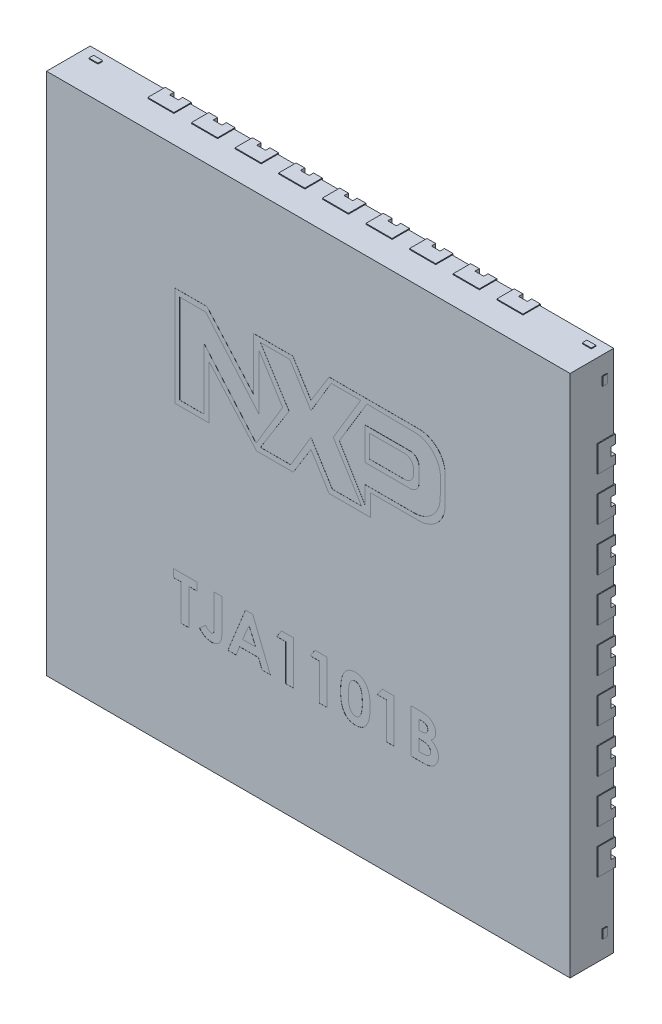
SolidWorks part; units mm, degrees
ref_plane "Front Plane" through (0, 0, 0) normal (0, 0, 1) x (1, 0, 0)
ref_plane "Top Plane" through (0, 0, 0) normal (0, 1, 0) x (1, 0, 0)
ref_plane "Right Plane" through (0, 0, 0) normal (1, 0, 0) x (0, 0, -1)
sketch "Sketch1" plane through (0, 0, 0) normal (0, 0, 1) x (1, 0, 0)
  line L1 (3, -3) -> (-3, -3)
  line L2 (3, -3) -> (3, 3)
  line L3 (3, 3) -> (-3, 3)
  line L4 (-3, -3) -> (-3, 3)
  line L5 (3, -3) -> (-3, 3) construction
  line L6 (3, 3) -> (-3, -3) construction
  point P0 (0, 0)
  dimension "D1" = 6
  dimension "D2" = 6
extrude "Boss-Extrude1" add sketch "Sketch1" along normal blind 0.5
sketch "Sketch3" plane through (0, 0, 0.5) normal (0, 0, 1) x (1, 0, 0)
  line L1 (-1.8824, 1.9808) -> (1.8824, 1.9808)
  line L2 (-1.8824, 1.9808) -> (-1.8824, -1.9808)
  line L3 (-1.8824, -1.9808) -> (1.8824, -1.9808)
  line L4 (1.8824, 1.9808) -> (1.8824, -1.9808)
  line L5 (-1.8824, 1.9808) -> (1.8824, -1.9808) construction
  line L6 (-1.8824, -1.9808) -> (1.8824, 1.9808) construction
  point P0 (0, 0)
sketch "Sketch4" plane through (0, 0, 0) normal (0, 0, -1) x (-1, 0, 0)
  line L0 (1.8824, 1.9808) -> (-1.8824, 1.9808) construction
  line L1 (-1.6324, 1.9808) -> (1.6324, 1.9808)
  line L2 (-1.8824, 1.7308) -> (-1.8824, -1.7308)
  line L3 (-1.6324, -1.9808) -> (1.6324, -1.9808)
  line L5 (-1.8824, 1.9808) -> (1.8824, -1.9808) construction
  line L6 (-1.8824, -1.9808) -> (1.8824, 1.9808) construction
  line L7 (-1.8824, 1.9808) -> (-1.8824, -1.9808) construction
  line L8 (1.8824, 1.7308) -> (1.8824, 1.4732)
  line L9 (1.8824, 1.9808) -> (1.8824, -1.9808) construction
  line L10 (1.8824, 0.8432) -> (1.8824, -1.7308)
  arc A0 (1.6324, -1.9808) -> (1.8824, -1.7308) centre (1.6324, -1.7308) ccw
  arc A1 (-1.8824, -1.7308) -> (-1.6324, -1.9808) centre (-1.6324, -1.7308) ccw
  arc A2 (1.6324, 1.9808) -> (1.8824, 1.7308) centre (1.6324, 1.7308) cw
  arc A3 (-1.6324, 1.9808) -> (-1.8824, 1.7308) centre (-1.6324, 1.7308) ccw
  arc A4 (1.8127, 1.3779) -> (1.8127, 0.9385) centre (1.8824, 1.1582) ccw
  arc A5 (1.8127, 0.9385) -> (1.8824, 0.8432) centre (1.7824, 0.8432) cw
  arc A6 (1.8824, 1.4732) -> (1.8127, 1.3779) centre (1.7824, 1.4732) cw
  point P0 (0, 0)
  point P29 (1.8824, 0.9277)
  point P32 (1.8824, 1.3887)
  dimension "D3" = 0.25
  dimension "D4" = 0.1
  dimension "D1" = 0
  dimension "D2" = 0
extrude "Cut-Extrude2" cut sketch "Sketch4" against normal blind 0.001
sketch "Sketch6" plane through (0, 0, 0.5) normal (0, 0, 1) x (1, 0, 0)
  line L0 (70.7212, 256.7277) -> (518.7212, 256.7277) construction
  line L1 (-1.5243, 0.4405) -> (-1.5243, 1.584)
  line L2 (-1.5243, 1.584) -> (-1.1608, 1.584)
  line L3 (-1.1608, 1.584) -> (-0.6294, 0.983)
  line L4 (-0.6294, 0.983) -> (-0.6294, 1.584)
  line L5 (-0.6294, 1.584) -> (-0.1766, 1.584)
  line L6 (-0.1766, 1.584) -> (0.0315, 1.2485)
  line L7 (0.0315, 1.2485) -> (0.2387, 1.584)
  line L8 (0.2387, 1.584) -> (1.269, 1.584)
  line L9 (1.569, 1.284) -> (1.569, 0.9732)
  line L10 (1.269, 0.6732) -> (0.7132, 0.6732)
  line L11 (0.7132, 0.6732) -> (0.7132, 0.4288)
  line L12 (0.7132, 0.4288) -> (0.2387, 0.4288)
  line L13 (0.2387, 0.4288) -> (0.0315, 0.7628)
  line L14 (0.0315, 0.7628) -> (-0.1711, 0.4347)
  line L15 (-0.1711, 0.4347) -> (-0.5917, 0.4347)
  line L16 (-0.5917, 0.4347) -> (-1.1363, 1.0506)
  line L17 (-1.1363, 1.0506) -> (-1.1363, 0.4405)
  line L18 (-1.1363, 0.4405) -> (-1.5243, 0.4405)
  line L19 (-1.4732, 0.4992) -> (-1.4732, 1.5224)
  line L20 (-1.4732, 1.5224) -> (-1.1742, 1.5224)
  line L21 (-1.1742, 1.5224) -> (-0.5652, 0.815)
  line L22 (-0.5652, 0.815) -> (-0.5652, 1.4509)
  line L23 (-0.5652, 1.4509) -> (-0.2935, 1.0155)
  line L24 (-0.2935, 1.0155) -> (-0.5981, 0.5087)
  line L25 (-0.5981, 0.5087) -> (-1.1917, 1.1983)
  line L26 (-1.1917, 1.1983) -> (-1.1917, 0.4992)
  line L27 (-1.1917, 0.4992) -> (-1.4732, 0.4992)
  line L28 (-0.5484, 1.5343) -> (-0.2103, 1.5343)
  line L29 (-0.2103, 1.5343) -> (0.0315, 1.1473)
  line L30 (0.0315, 1.1473) -> (0.2635, 1.5343)
  line L31 (0.2635, 1.5343) -> (0.6011, 1.5343)
  line L32 (0.6011, 1.5343) -> (0.2868, 1.0101)
  line L33 (0.2868, 1.0101) -> (0.6118, 0.4899)
  line L34 (0.6118, 0.4899) -> (0.2765, 0.4899)
  line L35 (0.2765, 0.4899) -> (0.0315, 0.882)
  line L36 (0.0315, 0.882) -> (-0.2015, 0.4933)
  line L37 (-0.2015, 0.4933) -> (-0.5484, 0.4933)
  line L38 (-0.5484, 0.4933) -> (-0.2196, 1.0155)
  line L39 (-0.2196, 1.0155) -> (-0.5484, 1.5343)
  line L40 (0.6733, 1.5343) -> (1.2198, 1.5266)
  line L41 (1.5155, 1.2225) -> (1.5127, 1.0185)
  line L42 (1.2127, 0.7227) -> (0.6509, 0.7227)
  line L43 (0.6509, 0.7227) -> (0.6509, 0.5207)
  line L44 (0.6509, 0.5207) -> (0.3558, 1.0101)
  line L45 (0.3558, 1.0101) -> (0.6733, 1.5343)
  line L47 (0.6509, 1.3152) -> (1.169, 1.3152)
  line L48 (1.269, 1.2152) -> (1.269, 1.0433)
  line L49 (1.169, 0.9433) -> (0.6509, 0.9433)
  line L50 (0.6509, 1.3152) -> (0.6509, 0.9433)
  line L51 (0.7044, 1.2599) -> (1.1068, 1.2599)
  line L52 (0.7044, 1.2599) -> (0.7044, 1.0022)
  line L53 (0.7044, 1.0022) -> (1.1068, 1.0022)
  line L54 (1.2068, 1.1599) -> (1.2068, 1.1022)
  arc A0 (1.569, 0.9732) -> (1.269, 0.6732) centre (1.269, 0.9732) cw
  arc A1 (1.269, 1.584) -> (1.569, 1.284) centre (1.269, 1.284) cw
  arc A2 (1.5127, 1.0185) -> (1.2127, 0.7227) centre (1.2127, 1.0227) cw
  arc A3 (1.2198, 1.5266) -> (1.5155, 1.2225) centre (1.2156, 1.2267) cw
  arc A4 (1.1068, 1.0022) -> (1.2068, 1.1022) centre (1.1068, 1.1022) ccw
  arc A5 (1.1068, 1.2599) -> (1.2068, 1.1599) centre (1.1068, 1.1599) cw
  arc A6 (1.269, 1.0433) -> (1.169, 0.9433) centre (1.169, 1.0433) cw
  arc A7 (1.169, 1.3152) -> (1.269, 1.2152) centre (1.169, 1.2152) cw
  dimension "D1" = 0.3
  dimension "D2" = 0.3
  dimension "D3" = 0.1
extrude "Boss-Extrude2" add sketch "Sketch6" along normal blind 0.001 contours A1 L8 L7 L6 L5 L4 L3 L2 L1 L18 L17 L16 L15 L14 L13 L12 L11 L10 A0 L9 L38 L39 L28 L29 L30 L31 L32 L33 L34 L35 L36 L37 L26 L27 L19 L20 L21 L22 L23 L24 L25 L40 A3 L41 A2 L42 L43 L44 | L52 L51 A5 L54 A4 L53 region at (-1.4913, 1.0122, 0.5)
sketch "Sketch8" plane through (0, 0, 0.5) normal (0, 0, 1) x (1, 0, 0)
  line L0 (-1.5539, -1.7085) -> (2.0877, -1.7085) construction
  text T0 "<b>TJA1101B</b>" font "Century Gothic" height 0.5
extrude "Cut-Extrude3" cut sketch "Sketch8" against normal blind 0.001
sketch "Sketch2" plane through (0, 0, 0) normal (0, 0, -1) x (-1, 0, 0)
  line L0 (-2, 2.65) -> (-2, 3.35) construction
  line L1 (-2.15, 2.65) -> (-2.15, 3.35)
  line L2 (-1.85, 2.65) -> (-1.85, 3.35)
  line L3 (-1.35, 2.65) -> (-1.35, 3.35)
  line L6 (-3, 3) -> (3, 3) construction
  line L7 (-1.65, 2.65) -> (-1.65, 3.35)
  line L8 (-1.5, 2.65) -> (-1.5, 3.35) construction
  line L9 (-0.85, 2.65) -> (-0.85, 3.35)
  line L10 (-1.15, 2.65) -> (-1.15, 3.35)
  line L11 (-1, 2.65) -> (-1, 3.35) construction
  line L12 (-0.35, 2.65) -> (-0.35, 3.35)
  line L13 (-0.65, 2.65) -> (-0.65, 3.35)
  line L14 (-0.5, 2.65) -> (-0.5, 3.35) construction
  line L15 (0.15, 2.65) -> (0.15, 3.35)
  line L16 (-0.15, 2.65) -> (-0.15, 3.35)
  line L17 (0, 2.65) -> (0, 3.35) construction
  line L18 (0.65, 2.65) -> (0.65, 3.35)
  line L19 (0.35, 2.65) -> (0.35, 3.35)
  line L20 (0.5, 2.65) -> (0.5, 3.35) construction
  line L21 (1.15, 2.65) -> (1.15, 3.35)
  line L22 (0.85, 2.65) -> (0.85, 3.35)
  line L23 (1, 2.65) -> (1, 3.35) construction
  line L24 (1.65, 2.65) -> (1.65, 3.35)
  line L25 (1.35, 2.65) -> (1.35, 3.35)
  line L26 (1.5, 2.65) -> (1.5, 3.35) construction
  line L27 (2.15, 2.65) -> (2.15, 3.35)
  line L28 (1.85, 2.65) -> (1.85, 3.35)
  line L29 (2, 2.65) -> (2, 3.35) construction
  line L30 (0, 0) -> (0, -1.6259) construction
  line L31 (0, 0) -> (1.65, 0) construction
  line L32 (-2, -2.65) -> (-2, -3.35) construction
  line L33 (-2.15, -2.65) -> (-2.15, -3.35)
  line L34 (-1.85, -2.65) -> (-1.85, -3.35)
  line L35 (-1.5, -2.65) -> (-1.5, -3.35) construction
  line L36 (-1.65, -2.65) -> (-1.65, -3.35)
  line L37 (-1.35, -2.65) -> (-1.35, -3.35)
  line L38 (-1, -2.65) -> (-1, -3.35) construction
  line L39 (-1.15, -2.65) -> (-1.15, -3.35)
  line L40 (-0.85, -2.65) -> (-0.85, -3.35)
  line L41 (-0.5, -2.65) -> (-0.5, -3.35) construction
  line L42 (-0.65, -2.65) -> (-0.65, -3.35)
  line L43 (-0.35, -2.65) -> (-0.35, -3.35)
  line L44 (0, -2.65) -> (0, -3.35) construction
  line L45 (-0.15, -2.65) -> (-0.15, -3.35)
  line L46 (0.15, -2.65) -> (0.15, -3.35)
  line L47 (0.5, -2.65) -> (0.5, -3.35) construction
  line L48 (0.35, -2.65) -> (0.35, -3.35)
  line L49 (0.65, -2.65) -> (0.65, -3.35)
  line L50 (1, -2.65) -> (1, -3.35) construction
  line L51 (0.85, -2.65) -> (0.85, -3.35)
  line L52 (1.15, -2.65) -> (1.15, -3.35)
  line L53 (1.5, -2.65) -> (1.5, -3.35) construction
  line L54 (1.35, -2.65) -> (1.35, -3.35)
  line L55 (1.65, -2.65) -> (1.65, -3.35)
  line L56 (2, -2.65) -> (2, -3.35) construction
  line L57 (1.85, -2.65) -> (1.85, -3.35)
  line L58 (2.15, -2.65) -> (2.15, -3.35)
  line L59 (2.65, 2) -> (3.35, 2) construction
  line L61 (-2.65, 2) -> (-3.35, 2) construction
  line L62 (-2.65, 2.15) -> (-3.35, 2.15)
  line L63 (-2.65, 1.85) -> (-3.35, 1.85)
  line L64 (-2.65, 1.5) -> (-3.35, 1.5) construction
  line L65 (-2.65, 1.65) -> (-3.35, 1.65)
  line L66 (-2.65, 1.35) -> (-3.35, 1.35)
  line L67 (-2.65, 1) -> (-3.35, 1) construction
  line L68 (-2.65, 1.15) -> (-3.35, 1.15)
  line L69 (-2.65, 0.85) -> (-3.35, 0.85)
  line L70 (-2.65, 0.5) -> (-3.35, 0.5) construction
  line L71 (-2.65, 0.65) -> (-3.35, 0.65)
  line L72 (-2.65, 0.35) -> (-3.35, 0.35)
  line L73 (-2.65, 0) -> (-3.35, 0) construction
  line L74 (-2.65, 0.15) -> (-3.35, 0.15)
  line L75 (-2.65, -0.15) -> (-3.35, -0.15)
  line L76 (-2.65, -0.5) -> (-3.35, -0.5) construction
  line L77 (-2.65, -0.35) -> (-3.35, -0.35)
  line L78 (-2.65, -0.65) -> (-3.35, -0.65)
  line L79 (-2.65, -1) -> (-3.35, -1) construction
  line L80 (-2.65, -0.85) -> (-3.35, -0.85)
  line L81 (-2.65, -1.15) -> (-3.35, -1.15)
  line L82 (-2.65, -1.5) -> (-3.35, -1.5) construction
  line L83 (-2.65, -1.35) -> (-3.35, -1.35)
  line L84 (-2.65, -1.65) -> (-3.35, -1.65)
  line L85 (-2.65, -2) -> (-3.35, -2) construction
  line L86 (-2.65, -1.85) -> (-3.35, -1.85)
  line L87 (-2.65, -2.15) -> (-3.35, -2.15)
  line L88 (2.65, 2.15) -> (3.35, 2.15)
  line L89 (2.65, 1.85) -> (3.35, 1.85)
  line L90 (2.65, 1.5) -> (3.35, 1.5) construction
  line L91 (2.65, 1.65) -> (3.35, 1.65)
  line L92 (2.65, 1.35) -> (3.35, 1.35)
  line L93 (2.65, 1) -> (3.35, 1) construction
  line L94 (2.65, 1.15) -> (3.35, 1.15)
  line L95 (2.65, 0.85) -> (3.35, 0.85)
  line L96 (2.65, 0.5) -> (3.35, 0.5) construction
  line L97 (2.65, 0.65) -> (3.35, 0.65)
  line L98 (2.65, 0.35) -> (3.35, 0.35)
  line L99 (2.65, 0) -> (3.35, 0) construction
  line L100 (2.65, 0.15) -> (3.35, 0.15)
  line L101 (2.65, -0.15) -> (3.35, -0.15)
  line L102 (2.65, -0.5) -> (3.35, -0.5) construction
  line L103 (2.65, -0.35) -> (3.35, -0.35)
  line L104 (2.65, -0.65) -> (3.35, -0.65)
  line L105 (2.65, -1) -> (3.35, -1) construction
  line L106 (2.65, -0.85) -> (3.35, -0.85)
  line L107 (2.65, -1.15) -> (3.35, -1.15)
  line L108 (2.65, -1.5) -> (3.35, -1.5) construction
  line L109 (2.65, -1.35) -> (3.35, -1.35)
  line L110 (2.65, -1.65) -> (3.35, -1.65)
  line L111 (2.65, -2) -> (3.35, -2) construction
  line L112 (2.65, -1.85) -> (3.35, -1.85)
  line L113 (2.65, -2.15) -> (3.35, -2.15)
  arc A0 (-2.15, 2.65) -> (-1.85, 2.65) centre (-2, 2.65) ccw
  arc A1 (-1.85, 3.35) -> (-2.15, 3.35) centre (-2, 3.35) ccw
  arc A4 (-1.65, 2.65) -> (-1.35, 2.65) centre (-1.5, 2.65) ccw
  arc A5 (-1.35, 3.35) -> (-1.65, 3.35) centre (-1.5, 3.35) ccw
  arc A6 (-1.15, 2.65) -> (-0.85, 2.65) centre (-1, 2.65) ccw
  arc A7 (-0.85, 3.35) -> (-1.15, 3.35) centre (-1, 3.35) ccw
  arc A8 (-0.65, 2.65) -> (-0.35, 2.65) centre (-0.5, 2.65) ccw
  arc A9 (-0.35, 3.35) -> (-0.65, 3.35) centre (-0.5, 3.35) ccw
  arc A10 (-0.15, 2.65) -> (0.15, 2.65) centre (0, 2.65) ccw
  arc A11 (0.15, 3.35) -> (-0.15, 3.35) centre (0, 3.35) ccw
  arc A12 (0.35, 2.65) -> (0.65, 2.65) centre (0.5, 2.65) ccw
  arc A13 (0.65, 3.35) -> (0.35, 3.35) centre (0.5, 3.35) ccw
  arc A14 (0.85, 2.65) -> (1.15, 2.65) centre (1, 2.65) ccw
  arc A15 (1.15, 3.35) -> (0.85, 3.35) centre (1, 3.35) ccw
  arc A16 (1.35, 2.65) -> (1.65, 2.65) centre (1.5, 2.65) ccw
  arc A17 (1.65, 3.35) -> (1.35, 3.35) centre (1.5, 3.35) ccw
  arc A18 (1.85, 2.65) -> (2.15, 2.65) centre (2, 2.65) ccw
  arc A19 (2.15, 3.35) -> (1.85, 3.35) centre (2, 3.35) ccw
  arc A20 (-2.15, -2.65) -> (-1.85, -2.65) centre (-2, -2.65) cw
  arc A21 (-1.85, -3.35) -> (-2.15, -3.35) centre (-2, -3.35) cw
  arc A22 (-1.65, -2.65) -> (-1.35, -2.65) centre (-1.5, -2.65) cw
  arc A23 (-1.35, -3.35) -> (-1.65, -3.35) centre (-1.5, -3.35) cw
  arc A24 (-1.15, -2.65) -> (-0.85, -2.65) centre (-1, -2.65) cw
  arc A25 (-0.85, -3.35) -> (-1.15, -3.35) centre (-1, -3.35) cw
  arc A26 (-0.65, -2.65) -> (-0.35, -2.65) centre (-0.5, -2.65) cw
  arc A27 (-0.35, -3.35) -> (-0.65, -3.35) centre (-0.5, -3.35) cw
  arc A28 (-0.15, -2.65) -> (0.15, -2.65) centre (0, -2.65) cw
  arc A29 (0.15, -3.35) -> (-0.15, -3.35) centre (0, -3.35) cw
  arc A30 (0.35, -2.65) -> (0.65, -2.65) centre (0.5, -2.65) cw
  arc A31 (0.65, -3.35) -> (0.35, -3.35) centre (0.5, -3.35) cw
  arc A32 (0.85, -2.65) -> (1.15, -2.65) centre (1, -2.65) cw
  arc A33 (1.15, -3.35) -> (0.85, -3.35) centre (1, -3.35) cw
  arc A34 (1.35, -2.65) -> (1.65, -2.65) centre (1.5, -2.65) cw
  arc A35 (1.65, -3.35) -> (1.35, -3.35) centre (1.5, -3.35) cw
  arc A36 (1.85, -2.65) -> (2.15, -2.65) centre (2, -2.65) cw
  arc A37 (2.15, -3.35) -> (1.85, -3.35) centre (2, -3.35) cw
  arc A38 (-2.65, 2.15) -> (-2.65, 1.85) centre (-2.65, 2) cw
  arc A39 (-3.35, 1.85) -> (-3.35, 2.15) centre (-3.35, 2) cw
  arc A40 (-2.65, 1.65) -> (-2.65, 1.35) centre (-2.65, 1.5) cw
  arc A41 (-3.35, 1.35) -> (-3.35, 1.65) centre (-3.35, 1.5) cw
  arc A42 (-2.65, 1.15) -> (-2.65, 0.85) centre (-2.65, 1) cw
  arc A43 (-3.35, 0.85) -> (-3.35, 1.15) centre (-3.35, 1) cw
  arc A44 (-2.65, 0.65) -> (-2.65, 0.35) centre (-2.65, 0.5) cw
  arc A45 (-3.35, 0.35) -> (-3.35, 0.65) centre (-3.35, 0.5) cw
  arc A46 (-2.65, 0.15) -> (-2.65, -0.15) centre (-2.65, 0) cw
  arc A47 (-3.35, -0.15) -> (-3.35, 0.15) centre (-3.35, 0) cw
  arc A48 (-2.65, -0.35) -> (-2.65, -0.65) centre (-2.65, -0.5) cw
  arc A49 (-3.35, -0.65) -> (-3.35, -0.35) centre (-3.35, -0.5) cw
  arc A50 (-2.65, -0.85) -> (-2.65, -1.15) centre (-2.65, -1) cw
  arc A51 (-3.35, -1.15) -> (-3.35, -0.85) centre (-3.35, -1) cw
  arc A52 (-2.65, -1.35) -> (-2.65, -1.65) centre (-2.65, -1.5) cw
  arc A53 (-3.35, -1.65) -> (-3.35, -1.35) centre (-3.35, -1.5) cw
  arc A54 (-2.65, -1.85) -> (-2.65, -2.15) centre (-2.65, -2) cw
  arc A55 (-3.35, -2.15) -> (-3.35, -1.85) centre (-3.35, -2) cw
  arc A56 (2.65, 2.15) -> (2.65, 1.85) centre (2.65, 2) ccw
  arc A57 (3.35, 1.85) -> (3.35, 2.15) centre (3.35, 2) ccw
  arc A58 (2.65, 1.65) -> (2.65, 1.35) centre (2.65, 1.5) ccw
  arc A59 (3.35, 1.35) -> (3.35, 1.65) centre (3.35, 1.5) ccw
  arc A60 (2.65, 1.15) -> (2.65, 0.85) centre (2.65, 1) ccw
  arc A61 (3.35, 0.85) -> (3.35, 1.15) centre (3.35, 1) ccw
  arc A62 (2.65, 0.65) -> (2.65, 0.35) centre (2.65, 0.5) ccw
  arc A63 (3.35, 0.35) -> (3.35, 0.65) centre (3.35, 0.5) ccw
  arc A64 (2.65, 0.15) -> (2.65, -0.15) centre (2.65, 0) ccw
  arc A65 (3.35, -0.15) -> (3.35, 0.15) centre (3.35, 0) ccw
  arc A66 (2.65, -0.35) -> (2.65, -0.65) centre (2.65, -0.5) ccw
  arc A67 (3.35, -0.65) -> (3.35, -0.35) centre (3.35, -0.5) ccw
  arc A68 (2.65, -0.85) -> (2.65, -1.15) centre (2.65, -1) ccw
  arc A69 (3.35, -1.15) -> (3.35, -0.85) centre (3.35, -1) ccw
  arc A70 (2.65, -1.35) -> (2.65, -1.65) centre (2.65, -1.5) ccw
  arc A71 (3.35, -1.65) -> (3.35, -1.35) centre (3.35, -1.5) ccw
  arc A72 (2.65, -1.85) -> (2.65, -2.15) centre (2.65, -2) ccw
  arc A73 (3.35, -2.15) -> (3.35, -1.85) centre (3.35, -2) ccw
  point P2 (-2, 3)
  point P10 (-1.5, 3)
  point P16 (-2, 2.5)
  point P21 (-1, 3)
  point P28 (-0.5, 3)
  point P35 (0, 3)
  point P42 (0.5, 3)
  point P49 (1, 3)
  point P56 (1.5, 3)
  point P63 (2, 3)
  point P72 (-2, -3)
  point P79 (-1.5, -3)
  point P86 (-1, -3)
  point P93 (-0.5, -3)
  point P100 (0, -3)
  point P107 (0.5, -3)
  point P114 (1, -3)
  point P121 (1.5, -3)
  point P128 (2, -3)
  point P136 (3, 2)
  point P140 (-3, 2)
  point P147 (-3, 1.5)
  point P154 (-3, 1)
  point P161 (-3, 0.5)
  point P168 (-3, 0)
  point P175 (-3, -0.5)
  point P182 (-3, -1)
  point P189 (-3, -1.5)
  point P196 (-3, -2)
  point P206 (3, 1.5)
  point P213 (3, 1)
  point P220 (3, 0.5)
  point P227 (3, 0)
  point P234 (3, -0.5)
  point P241 (3, -1)
  point P248 (3, -1.5)
  point P255 (3, -2)
  dimension "D1" = 0.3
  dimension "D2" = 9
  dimension "D4" = 0
  dimension "D5" = 0.5
  dimension "D8" = 2
sketch "Sketch10" plane through (0, 0, 0.5) normal (0, 0, 1) x (1, 0, 0)
  line L0 (0.6509, 1.3152) -> (1.169, 1.3152)
  line L1 (0.6509, 1.3152) -> (0.6509, 0.9433)
  line L2 (0.6509, 0.9433) -> (1.169, 0.9433)
  line L3 (1.269, 1.2152) -> (1.269, 1.0433)
  line L4 (1.2068, 1.1599) -> (1.2068, 1.1022)
  line L5 (1.1068, 1.2599) -> (0.7044, 1.2599)
  line L6 (0.7044, 1.2599) -> (0.7044, 1.0022)
  line L7 (0.7044, 1.0022) -> (1.1068, 1.0022)
  arc A0 (1.169, 1.3152) -> (1.269, 1.2152) centre (1.169, 1.2152) cw
  arc A1 (1.269, 1.0433) -> (1.169, 0.9433) centre (1.169, 1.0433) cw
  arc A2 (1.2068, 1.1022) -> (1.1068, 1.0022) centre (1.1068, 1.1022) cw
  arc A3 (1.1068, 1.2599) -> (1.2068, 1.1599) centre (1.1068, 1.1599) cw
extrude "Boss-Extrude3" add sketch "Sketch10" along normal blind 0.002
extrude "Boss-Extrude4" add sketch "Sketch2" along normal blind 0.01
sketch "Sketch11" plane through (0, 0, 0.5) normal (0, 0, 1) x (1, 0, 0)
  line L1 (-3, 3) -> (3, 3)
  line L2 (-3, 3) -> (-3, -3)
  line L3 (-3, -3) -> (3, -3)
  line L4 (3, 3) -> (3, -3)
  line L5 (-4.69, 4.3097) -> (4.6689, 4.3097)
  line L6 (-4.69, 4.3097) -> (-4.69, -5.1125)
  line L7 (-4.69, -5.1125) -> (4.6689, -5.1125)
  line L8 (4.6689, 4.3097) -> (4.6689, -5.1125)
extrude "Cut-Extrude4" cut sketch "Sketch11" against normal blind 10.01
sketch "Sketch12" plane through (0, 0, -0.01) normal (0, 0, -1) x (-1, 0, 0)
  line L0 (-3, 3) -> (-1.6807, 1.6807) construction
  line L1 (-3, 3) -> (-2.15, 3) construction
  line L2 (0, 0) -> (0.5, 0) construction
  line L3 (0, 0) -> (0, 0.8589) construction
  circle A0 centre (-2, 2.65) radius 0.025
  circle A1 centre (-1.5, 2.65) radius 0.025
  circle A2 centre (-1, 2.65) radius 0.025
  circle A3 centre (-0.5, 2.65) radius 0.025
  circle A4 centre (0, 2.65) radius 0.025
  circle A5 centre (0.5, 2.65) radius 0.025
  circle A6 centre (1, 2.65) radius 0.025
  circle A7 centre (1.5, 2.65) radius 0.025
  circle A8 centre (2, 2.65) radius 0.025
  circle A9 centre (-2.65, -2) radius 0.025
  circle A10 centre (-2.65, -1.5) radius 0.025
  circle A11 centre (-2.65, -1) radius 0.025
  circle A12 centre (-2.65, -0.5) radius 0.025
  circle A13 centre (-2.65, 0) radius 0.025
  circle A14 centre (-2.65, 0.5) radius 0.025
  circle A15 centre (-2.65, 1) radius 0.025
  circle A16 centre (-2.65, 1.5) radius 0.025
  circle A17 centre (-2.65, 2) radius 0.025
  circle A18 centre (2, -2.65) radius 0.025
  circle A19 centre (1.5, -2.65) radius 0.025
  circle A20 centre (1, -2.65) radius 0.025
  circle A21 centre (0.5, -2.65) radius 0.025
  circle A22 centre (0, -2.65) radius 0.025
  circle A23 centre (-0.5, -2.65) radius 0.025
  circle A24 centre (-1, -2.65) radius 0.025
  circle A25 centre (-1.5, -2.65) radius 0.025
  circle A26 centre (-2, -2.65) radius 0.025
  circle A27 centre (2.65, 2) radius 0.025
  circle A28 centre (2.65, 1.5) radius 0.025
  circle A29 centre (2.65, 1) radius 0.025
  circle A30 centre (2.65, 0.5) radius 0.025
  circle A31 centre (2.65, 0) radius 0.025
  circle A32 centre (2.65, -0.5) radius 0.025
  circle A33 centre (2.65, -1) radius 0.025
  circle A34 centre (2.65, -1.5) radius 0.025
  circle A35 centre (2.65, -2) radius 0.025
  dimension "D1" = 0.05
  dimension "D3" = 45
  dimension "D2" = 9
sketch "Sketch14" plane through (0, -3, 0) normal (0, -1, 0) x (1, 0, 0)
  line L0 (-1.85, -0.01) -> (-1.85, 0) construction
  line L1 (-2.15, -0.01) -> (-1.85, -0.01)
  line L2 (-2.15, -0.01) -> (-2.15, 0.19)
  line L3 (-2.15, 0.19) -> (-1.85, 0.19)
  line L4 (-1.85, -0.01) -> (-1.85, 0.19)
  line L5 (-1.65, -0.01) -> (-1.65, 0.19)
  line L6 (-1.65, -0.01) -> (-1.35, -0.01)
  line L7 (-1.35, -0.01) -> (-1.35, 0.19)
  line L8 (-1.65, 0.19) -> (-1.35, 0.19)
  line L9 (-1.15, -0.01) -> (-1.15, 0.19)
  line L10 (-1.15, -0.01) -> (-0.85, -0.01)
  line L11 (-0.85, -0.01) -> (-0.85, 0.19)
  line L12 (-1.15, 0.19) -> (-0.85, 0.19)
  line L13 (-0.65, -0.01) -> (-0.65, 0.19)
  line L14 (-0.65, -0.01) -> (-0.35, -0.01)
  line L15 (-0.35, -0.01) -> (-0.35, 0.19)
  line L16 (-0.65, 0.19) -> (-0.35, 0.19)
  line L17 (-0.15, -0.01) -> (-0.15, 0.19)
  line L18 (-0.15, -0.01) -> (0.15, -0.01)
  line L19 (0.15, -0.01) -> (0.15, 0.19)
  line L20 (-0.15, 0.19) -> (0.15, 0.19)
  line L21 (0.35, -0.01) -> (0.35, 0.19)
  line L22 (0.35, -0.01) -> (0.65, -0.01)
  line L23 (0.65, -0.01) -> (0.65, 0.19)
  line L24 (0.35, 0.19) -> (0.65, 0.19)
  line L25 (0.85, -0.01) -> (0.85, 0.19)
  line L26 (0.85, -0.01) -> (1.15, -0.01)
  line L27 (1.15, -0.01) -> (1.15, 0.19)
  line L28 (0.85, 0.19) -> (1.15, 0.19)
  line L29 (1.35, -0.01) -> (1.35, 0.19)
  line L30 (1.35, -0.01) -> (1.65, -0.01)
  line L31 (1.65, -0.01) -> (1.65, 0.19)
  line L32 (1.35, 0.19) -> (1.65, 0.19)
  line L33 (1.85, -0.01) -> (1.85, 0.19)
  line L34 (1.85, -0.01) -> (2.15, -0.01)
  line L35 (2.15, -0.01) -> (2.15, 0.19)
  line L36 (1.85, 0.19) -> (2.15, 0.19)
  dimension "D1" = 0
  dimension "D2" = 0.2
  dimension "D3" = 9
extrude "Boss-Extrude5" add sketch "Sketch14" along normal blind 0.01
sketch "Sketch15" plane through (-3, 0, 0) normal (-1, 0, 0) x (0, 0, 1)
  line L0 (-0.01, -1.65) -> (-0.01, -1.35)
  line L1 (-0.01, -2.15) -> (0.19, -2.15)
  line L2 (-0.01, -2.15) -> (-0.01, -1.85)
  line L3 (-0.01, -1.85) -> (0.19, -1.85)
  line L4 (0.19, -2.15) -> (0.19, -1.85)
  line L5 (-0.01, -1.65) -> (0.19, -1.65)
  line L6 (0.19, -1.65) -> (0.19, -1.35)
  line L7 (-0.01, -1.35) -> (0.19, -1.35)
  line L8 (-0.01, -1.15) -> (-0.01, -0.85)
  line L9 (-0.01, -1.15) -> (0.19, -1.15)
  line L10 (0.19, -1.15) -> (0.19, -0.85)
  line L11 (-0.01, -0.85) -> (0.19, -0.85)
  line L12 (-0.01, -0.65) -> (-0.01, -0.35)
  line L13 (-0.01, -0.65) -> (0.19, -0.65)
  line L14 (0.19, -0.65) -> (0.19, -0.35)
  line L15 (-0.01, -0.35) -> (0.19, -0.35)
  line L16 (-0.01, -0.15) -> (-0.01, 0.15)
  line L17 (-0.01, -0.15) -> (0.19, -0.15)
  line L18 (0.19, -0.15) -> (0.19, 0.15)
  line L19 (-0.01, 0.15) -> (0.19, 0.15)
  line L20 (-0.01, 0.35) -> (-0.01, 0.65)
  line L21 (-0.01, 0.35) -> (0.19, 0.35)
  line L22 (0.19, 0.35) -> (0.19, 0.65)
  line L23 (-0.01, 0.65) -> (0.19, 0.65)
  line L24 (-0.01, 0.85) -> (-0.01, 1.15)
  line L25 (-0.01, 0.85) -> (0.19, 0.85)
  line L26 (0.19, 0.85) -> (0.19, 1.15)
  line L27 (-0.01, 1.15) -> (0.19, 1.15)
  line L28 (-0.01, 1.35) -> (-0.01, 1.65)
  line L29 (-0.01, 1.35) -> (0.19, 1.35)
  line L30 (0.19, 1.35) -> (0.19, 1.65)
  line L31 (-0.01, 1.65) -> (0.19, 1.65)
  line L32 (-0.01, 1.85) -> (-0.01, 2.15)
  line L33 (-0.01, 1.85) -> (0.19, 1.85)
  line L34 (0.19, 1.85) -> (0.19, 2.15)
  line L35 (-0.01, 2.15) -> (0.19, 2.15)
  dimension "D1" = 0
  dimension "D2" = 0.2
  dimension "D3" = 9
extrude "Boss-Extrude6" add sketch "Sketch15" along normal blind 0.01
mirror "Mirror1" about plane through (0, 0, 0) normal (1, 0, 0) of "Boss-Extrude6"
mirror "Mirror2" about plane through (0, 0, 0) normal (0, 1, 0) of "Boss-Extrude5"
sketch "Sketch16" plane through (0, 0, -0.01) normal (0, 0, -1) x (-1, 0, 0)
  line L0 (-2, 3.06) -> (-2, 2.96) construction
  line L1 (-1.85, 3.01) -> (-2.15, 3.01) construction
  line L2 (-1.95, 3.06) -> (-1.95, 2.96)
  line L3 (-2.05, 3.06) -> (-2.05, 2.96)
  line L4 (-1.55, 3.06) -> (-1.55, 2.96)
  line L5 (-1.45, 3.06) -> (-1.45, 2.96)
  line L6 (-1.5, 3.06) -> (-1.5, 2.96) construction
  line L7 (-1.05, 3.06) -> (-1.05, 2.96)
  line L8 (-0.95, 3.06) -> (-0.95, 2.96)
  line L9 (-1, 3.06) -> (-1, 2.96) construction
  line L10 (-0.55, 3.06) -> (-0.55, 2.96)
  line L11 (-0.45, 3.06) -> (-0.45, 2.96)
  line L12 (-0.5, 3.06) -> (-0.5, 2.96) construction
  line L13 (-0.05, 3.06) -> (-0.05, 2.96)
  line L14 (0.05, 3.06) -> (0.05, 2.96)
  line L15 (0, 3.06) -> (0, 2.96) construction
  line L16 (0.45, 3.06) -> (0.45, 2.96)
  line L17 (0.55, 3.06) -> (0.55, 2.96)
  line L18 (0.5, 3.06) -> (0.5, 2.96) construction
  line L19 (0.95, 3.06) -> (0.95, 2.96)
  line L20 (1.05, 3.06) -> (1.05, 2.96)
  line L21 (1, 3.06) -> (1, 2.96) construction
  line L22 (1.45, 3.06) -> (1.45, 2.96)
  line L23 (1.55, 3.06) -> (1.55, 2.96)
  line L24 (1.5, 3.06) -> (1.5, 2.96) construction
  line L25 (1.95, 3.06) -> (1.95, 2.96)
  line L26 (2.05, 3.06) -> (2.05, 2.96)
  line L27 (2, 3.06) -> (2, 2.96) construction
  line L28 (0, 0) -> (0.7795, 0) construction
  line L29 (0, 0) -> (0, 0.8504) construction
  line L30 (-2, -3.06) -> (-2, -2.96) construction
  line L31 (-1.95, -3.06) -> (-1.95, -2.96)
  line L32 (-2.05, -3.06) -> (-2.05, -2.96)
  line L33 (-1.5, -3.06) -> (-1.5, -2.96) construction
  line L34 (-1.45, -3.06) -> (-1.45, -2.96)
  line L35 (-1.55, -3.06) -> (-1.55, -2.96)
  line L36 (-1, -3.06) -> (-1, -2.96) construction
  line L37 (-0.95, -3.06) -> (-0.95, -2.96)
  line L38 (-1.05, -3.06) -> (-1.05, -2.96)
  line L39 (-0.5, -3.06) -> (-0.5, -2.96) construction
  line L40 (-0.45, -3.06) -> (-0.45, -2.96)
  line L41 (-0.55, -3.06) -> (-0.55, -2.96)
  line L42 (0, -3.06) -> (0, -2.96) construction
  line L43 (0.05, -3.06) -> (0.05, -2.96)
  line L44 (-0.05, -3.06) -> (-0.05, -2.96)
  line L45 (0.5, -3.06) -> (0.5, -2.96) construction
  line L46 (0.55, -3.06) -> (0.55, -2.96)
  line L47 (0.45, -3.06) -> (0.45, -2.96)
  line L48 (1, -3.06) -> (1, -2.96) construction
  line L49 (1.05, -3.06) -> (1.05, -2.96)
  line L50 (0.95, -3.06) -> (0.95, -2.96)
  line L51 (1.5, -3.06) -> (1.5, -2.96) construction
  line L52 (1.55, -3.06) -> (1.55, -2.96)
  line L53 (1.45, -3.06) -> (1.45, -2.96)
  line L54 (2, -3.06) -> (2, -2.96) construction
  line L55 (2.05, -3.06) -> (2.05, -2.96)
  line L56 (1.95, -3.06) -> (1.95, -2.96)
  line L57 (-3.06, 2) -> (-2.96, 2) construction
  line L58 (-3.01, 2.15) -> (-3.01, 1.85) construction
  line L59 (-3.06, 2.05) -> (-2.96, 2.05)
  line L60 (-3.06, 1.95) -> (-2.96, 1.95)
  line L61 (-3.06, 1.45) -> (-2.96, 1.45)
  line L62 (-3.06, 1.55) -> (-2.96, 1.55)
  line L63 (-3.06, 1.5) -> (-2.96, 1.5) construction
  line L64 (-3.06, 0.95) -> (-2.96, 0.95)
  line L65 (-3.06, 1.05) -> (-2.96, 1.05)
  line L66 (-3.06, 1) -> (-2.96, 1) construction
  line L67 (-3.06, 0.45) -> (-2.96, 0.45)
  line L68 (-3.06, 0.55) -> (-2.96, 0.55)
  line L69 (-3.06, 0.5) -> (-2.96, 0.5) construction
  line L70 (-3.06, -0.05) -> (-2.96, -0.05)
  line L71 (-3.06, 0.05) -> (-2.96, 0.05)
  line L72 (-3.06, 0) -> (-2.96, 0) construction
  line L73 (-3.06, -0.55) -> (-2.96, -0.55)
  line L74 (-3.06, -0.45) -> (-2.96, -0.45)
  line L75 (-3.06, -0.5) -> (-2.96, -0.5) construction
  line L76 (-3.06, -1.05) -> (-2.96, -1.05)
  line L77 (-3.06, -0.95) -> (-2.96, -0.95)
  line L78 (-3.06, -1) -> (-2.96, -1) construction
  line L79 (-3.06, -1.55) -> (-2.96, -1.55)
  line L80 (-3.06, -1.45) -> (-2.96, -1.45)
  line L81 (-3.06, -1.5) -> (-2.96, -1.5) construction
  line L82 (-3.06, -2.05) -> (-2.96, -2.05)
  line L83 (-3.06, -1.95) -> (-2.96, -1.95)
  line L84 (-3.06, -2) -> (-2.96, -2) construction
  line L85 (3.06, 2) -> (2.96, 2) construction
  line L86 (3.06, 2.05) -> (2.96, 2.05)
  line L87 (3.06, 1.95) -> (2.96, 1.95)
  line L88 (3.06, 1.5) -> (2.96, 1.5) construction
  line L89 (3.06, 1.55) -> (2.96, 1.55)
  line L90 (3.06, 1.45) -> (2.96, 1.45)
  line L91 (3.06, 1) -> (2.96, 1) construction
  line L92 (3.06, 1.05) -> (2.96, 1.05)
  line L93 (3.06, 0.95) -> (2.96, 0.95)
  line L94 (3.06, 0.5) -> (2.96, 0.5) construction
  line L95 (3.06, 0.55) -> (2.96, 0.55)
  line L96 (3.06, 0.45) -> (2.96, 0.45)
  line L97 (3.06, 0) -> (2.96, 0) construction
  line L98 (3.06, 0.05) -> (2.96, 0.05)
  line L99 (3.06, -0.05) -> (2.96, -0.05)
  line L100 (3.06, -0.5) -> (2.96, -0.5) construction
  line L101 (3.06, -0.45) -> (2.96, -0.45)
  line L102 (3.06, -0.55) -> (2.96, -0.55)
  line L103 (3.06, -1) -> (2.96, -1) construction
  line L104 (3.06, -0.95) -> (2.96, -0.95)
  line L105 (3.06, -1.05) -> (2.96, -1.05)
  line L106 (3.06, -1.5) -> (2.96, -1.5) construction
  line L107 (3.06, -1.45) -> (2.96, -1.45)
  line L108 (3.06, -1.55) -> (2.96, -1.55)
  line L109 (3.06, -2) -> (2.96, -2) construction
  line L110 (3.06, -1.95) -> (2.96, -1.95)
  line L111 (3.06, -2.05) -> (2.96, -2.05)
  arc A0 (-1.95, 3.06) -> (-2.05, 3.06) centre (-2, 3.06) ccw
  arc A1 (-2.05, 2.96) -> (-1.95, 2.96) centre (-2, 2.96) ccw
  arc A2 (-1.45, 3.06) -> (-1.55, 3.06) centre (-1.5, 3.06) ccw
  arc A3 (-1.55, 2.96) -> (-1.45, 2.96) centre (-1.5, 2.96) ccw
  arc A4 (-0.95, 3.06) -> (-1.05, 3.06) centre (-1, 3.06) ccw
  arc A5 (-1.05, 2.96) -> (-0.95, 2.96) centre (-1, 2.96) ccw
  arc A6 (-0.45, 3.06) -> (-0.55, 3.06) centre (-0.5, 3.06) ccw
  arc A7 (-0.55, 2.96) -> (-0.45, 2.96) centre (-0.5, 2.96) ccw
  arc A8 (0.05, 3.06) -> (-0.05, 3.06) centre (0, 3.06) ccw
  arc A9 (-0.05, 2.96) -> (0.05, 2.96) centre (0, 2.96) ccw
  arc A10 (0.55, 3.06) -> (0.45, 3.06) centre (0.5, 3.06) ccw
  arc A11 (0.45, 2.96) -> (0.55, 2.96) centre (0.5, 2.96) ccw
  arc A12 (1.05, 3.06) -> (0.95, 3.06) centre (1, 3.06) ccw
  arc A13 (0.95, 2.96) -> (1.05, 2.96) centre (1, 2.96) ccw
  arc A14 (1.55, 3.06) -> (1.45, 3.06) centre (1.5, 3.06) ccw
  arc A15 (1.45, 2.96) -> (1.55, 2.96) centre (1.5, 2.96) ccw
  arc A16 (2.05, 3.06) -> (1.95, 3.06) centre (2, 3.06) ccw
  arc A17 (1.95, 2.96) -> (2.05, 2.96) centre (2, 2.96) ccw
  arc A18 (-1.95, -3.06) -> (-2.05, -3.06) centre (-2, -3.06) cw
  arc A19 (-2.05, -2.96) -> (-1.95, -2.96) centre (-2, -2.96) cw
  arc A20 (-1.45, -3.06) -> (-1.55, -3.06) centre (-1.5, -3.06) cw
  arc A21 (-1.55, -2.96) -> (-1.45, -2.96) centre (-1.5, -2.96) cw
  arc A22 (-0.95, -3.06) -> (-1.05, -3.06) centre (-1, -3.06) cw
  arc A23 (-1.05, -2.96) -> (-0.95, -2.96) centre (-1, -2.96) cw
  arc A24 (-0.45, -3.06) -> (-0.55, -3.06) centre (-0.5, -3.06) cw
  arc A25 (-0.55, -2.96) -> (-0.45, -2.96) centre (-0.5, -2.96) cw
  arc A26 (0.05, -3.06) -> (-0.05, -3.06) centre (0, -3.06) cw
  arc A27 (-0.05, -2.96) -> (0.05, -2.96) centre (0, -2.96) cw
  arc A28 (0.55, -3.06) -> (0.45, -3.06) centre (0.5, -3.06) cw
  arc A29 (0.45, -2.96) -> (0.55, -2.96) centre (0.5, -2.96) cw
  arc A30 (1.05, -3.06) -> (0.95, -3.06) centre (1, -3.06) cw
  arc A31 (0.95, -2.96) -> (1.05, -2.96) centre (1, -2.96) cw
  arc A32 (1.55, -3.06) -> (1.45, -3.06) centre (1.5, -3.06) cw
  arc A33 (1.45, -2.96) -> (1.55, -2.96) centre (1.5, -2.96) cw
  arc A34 (2.05, -3.06) -> (1.95, -3.06) centre (2, -3.06) cw
  arc A35 (1.95, -2.96) -> (2.05, -2.96) centre (2, -2.96) cw
  arc A36 (-3.06, 2.05) -> (-3.06, 1.95) centre (-3.06, 2) ccw
  arc A37 (-2.96, 1.95) -> (-2.96, 2.05) centre (-2.96, 2) ccw
  arc A38 (-3.06, 1.55) -> (-3.06, 1.45) centre (-3.06, 1.5) ccw
  arc A39 (-2.96, 1.45) -> (-2.96, 1.55) centre (-2.96, 1.5) ccw
  arc A40 (-3.06, 1.05) -> (-3.06, 0.95) centre (-3.06, 1) ccw
  arc A41 (-2.96, 0.95) -> (-2.96, 1.05) centre (-2.96, 1) ccw
  arc A42 (-3.06, 0.55) -> (-3.06, 0.45) centre (-3.06, 0.5) ccw
  arc A43 (-2.96, 0.45) -> (-2.96, 0.55) centre (-2.96, 0.5) ccw
  arc A44 (-3.06, 0.05) -> (-3.06, -0.05) centre (-3.06, 0) ccw
  arc A45 (-2.96, -0.05) -> (-2.96, 0.05) centre (-2.96, 0) ccw
  arc A46 (-3.06, -0.45) -> (-3.06, -0.55) centre (-3.06, -0.5) ccw
  arc A47 (-2.96, -0.55) -> (-2.96, -0.45) centre (-2.96, -0.5) ccw
  arc A48 (-3.06, -0.95) -> (-3.06, -1.05) centre (-3.06, -1) ccw
  arc A49 (-2.96, -1.05) -> (-2.96, -0.95) centre (-2.96, -1) ccw
  arc A50 (-3.06, -1.45) -> (-3.06, -1.55) centre (-3.06, -1.5) ccw
  arc A51 (-2.96, -1.55) -> (-2.96, -1.45) centre (-2.96, -1.5) ccw
  arc A52 (-3.06, -1.95) -> (-3.06, -2.05) centre (-3.06, -2) ccw
  arc A53 (-2.96, -2.05) -> (-2.96, -1.95) centre (-2.96, -2) ccw
  arc A54 (3.06, 2.05) -> (3.06, 1.95) centre (3.06, 2) cw
  arc A55 (2.96, 1.95) -> (2.96, 2.05) centre (2.96, 2) cw
  arc A56 (3.06, 1.55) -> (3.06, 1.45) centre (3.06, 1.5) cw
  arc A57 (2.96, 1.45) -> (2.96, 1.55) centre (2.96, 1.5) cw
  arc A58 (3.06, 1.05) -> (3.06, 0.95) centre (3.06, 1) cw
  arc A59 (2.96, 0.95) -> (2.96, 1.05) centre (2.96, 1) cw
  arc A60 (3.06, 0.55) -> (3.06, 0.45) centre (3.06, 0.5) cw
  arc A61 (2.96, 0.45) -> (2.96, 0.55) centre (2.96, 0.5) cw
  arc A62 (3.06, 0.05) -> (3.06, -0.05) centre (3.06, 0) cw
  arc A63 (2.96, -0.05) -> (2.96, 0.05) centre (2.96, 0) cw
  arc A64 (3.06, -0.45) -> (3.06, -0.55) centre (3.06, -0.5) cw
  arc A65 (2.96, -0.55) -> (2.96, -0.45) centre (2.96, -0.5) cw
  arc A66 (3.06, -0.95) -> (3.06, -1.05) centre (3.06, -1) cw
  arc A67 (2.96, -1.05) -> (2.96, -0.95) centre (2.96, -1) cw
  arc A68 (3.06, -1.45) -> (3.06, -1.55) centre (3.06, -1.5) cw
  arc A69 (2.96, -1.55) -> (2.96, -1.45) centre (2.96, -1.5) cw
  arc A70 (3.06, -1.95) -> (3.06, -2.05) centre (3.06, -2) cw
  arc A71 (2.96, -2.05) -> (2.96, -1.95) centre (2.96, -2) cw
  point P4 (-2, 3.01)
  point P12 (-1.5, 3.01)
  point P19 (-1, 3.01)
  point P26 (-0.5, 3.01)
  point P33 (0, 3.01)
  point P40 (0.5, 3.01)
  point P47 (1, 3.01)
  point P54 (1.5, 3.01)
  point P61 (2, 3.01)
  point P71 (-2, -3.01)
  point P78 (-1.5, -3.01)
  point P85 (-1, -3.01)
  point P92 (-0.5, -3.01)
  point P99 (0, -3.01)
  point P106 (0.5, -3.01)
  point P113 (1, -3.01)
  point P120 (1.5, -3.01)
  point P127 (2, -3.01)
  point P136 (-3.01, 2)
  point P144 (-3.01, 1.5)
  point P151 (-3.01, 1)
  point P158 (-3.01, 0.5)
  point P165 (-3.01, 0)
  point P172 (-3.01, -0.5)
  point P179 (-3.01, -1)
  point P186 (-3.01, -1.5)
  point P193 (-3.01, -2)
  point P199 (3.01, 2)
  point P206 (3.01, 1.5)
  point P213 (3.01, 1)
  point P220 (3.01, 0.5)
  point P227 (3.01, 0)
  point P234 (3.01, -0.5)
  point P241 (3.01, -1)
  point P248 (3.01, -1.5)
  point P255 (3.01, -2)
  dimension "D3" = 0.05
  dimension "D4" = 0.05
  dimension "D1" = 0.05
  dimension "D5" = 0.05
  dimension "D2" = 9
  dimension "D6" = 9
extrude "Cut-Extrude6" cut sketch "Sketch16" against normal blind 0.05
sketch "Sketch17" plane through (0, 3, 0) normal (0, 1, 0) x (1, 0, 0)
  line L0 (0, 0) -> (0, 0.4871) construction
  line L1 (-2.8779, -0.0822) -> (-2.775, -0.0822)
  line L2 (-2.8779, -0.0822) -> (-2.8779, -0.1355)
  line L3 (-2.8779, -0.1355) -> (-2.775, -0.1355)
  line L4 (-2.775, -0.0822) -> (-2.775, -0.1355)
  line L5 (2.775, -0.0822) -> (2.775, -0.1355)
  line L6 (2.8779, -0.1355) -> (2.775, -0.1355)
  line L7 (2.8779, -0.0822) -> (2.8779, -0.1355)
  line L8 (2.8779, -0.0822) -> (2.775, -0.0822)
extrude "Boss-Extrude7" add sketch "Sketch17" along normal blind 0.01
mirror "Mirror3" about plane through (0, 0, 0) normal (0, 1, 0) of "Boss-Extrude7"
sketch "Sketch18" plane through (-3, 0, 0) normal (-1, 0, 0) x (0, 0, 1)
  line L0 (0, 0) -> (0.2423, 0) construction
  line L1 (0.0822, -2.6954) -> (0.1355, -2.6954)
  line L2 (0.0822, -2.6954) -> (0.0822, -2.7925)
  line L3 (0.0822, -2.7925) -> (0.1355, -2.7925)
  line L4 (0.1355, -2.6954) -> (0.1355, -2.7925)
  line L5 (0.1355, 2.6954) -> (0.1355, 2.7925)
  line L6 (0.0822, 2.7925) -> (0.1355, 2.7925)
  line L7 (0.0822, 2.6954) -> (0.0822, 2.7925)
  line L8 (0.0822, 2.6954) -> (0.1355, 2.6954)
  line L9 (0.1355, 3.01) -> (0.1355, 3) construction
  line L10 (0.0822, 3.01) -> (0.0822, 3) construction
  dimension "D1" = 0
  dimension "D2" = 0
extrude "Boss-Extrude8" add sketch "Sketch18" along normal blind 0.01
mirror "Mirror4" about plane through (0, 0, 0) normal (1, 0, 0) of "Boss-Extrude8"
